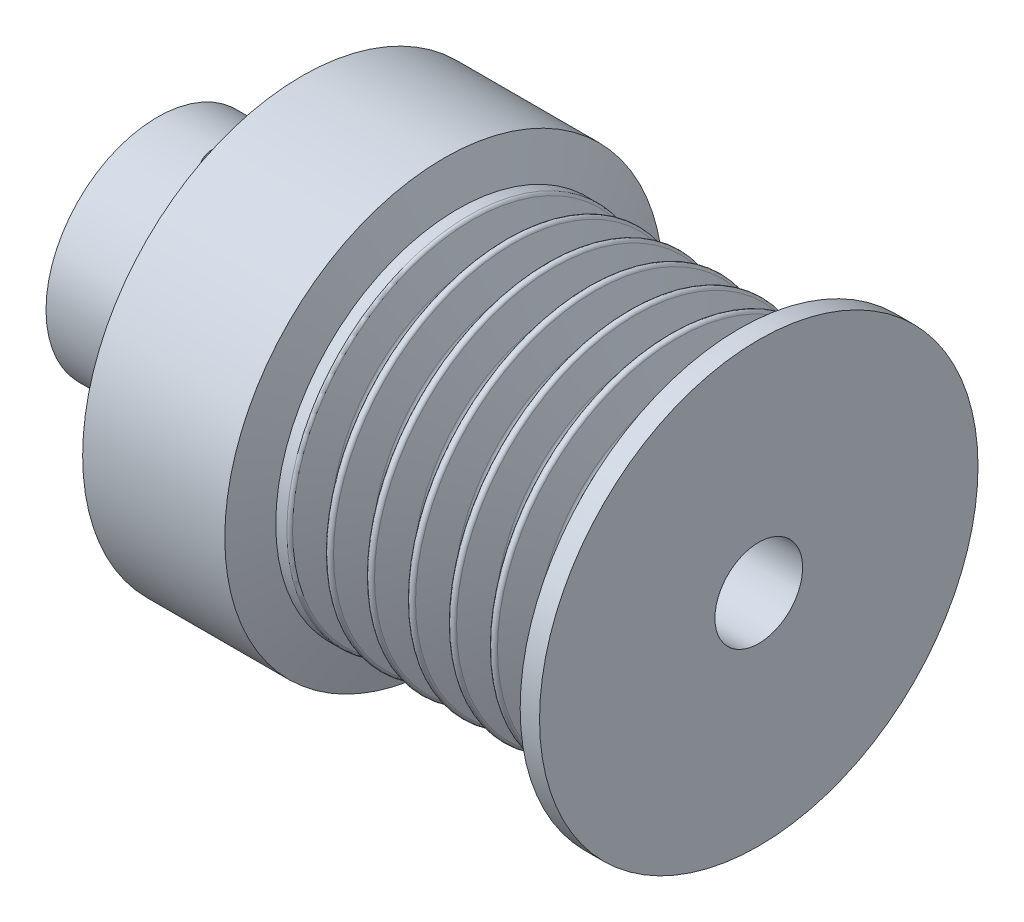
SolidWorks part; units mm, degrees
material "6061-T6 (SS)"
ref_plane "Front Plane" through (0, 0, 0) normal (0, 0, 1) x (1, 0, 0)
ref_plane "Top Plane" through (0, 0, 0) normal (0, 1, 0) x (1, 0, 0)
ref_plane "Right Plane" through (0, 0, 0) normal (1, 0, 0) x (0, 0, -1)
sketch "Sketch1" plane through (0, 0, 0) normal (0, 0, 1) x (1, 0, 0)
  line L0 (0, 0) -> (0, 2.5) construction
  line L1 (0, 2.5) -> (34.29, 2.5)
  line L2 (34.29, 2.5) -> (34.29, 12.5)
  line L3 (34.29, 12.5) -> (8.24, 12.5)
  line L4 (8.24, 12.5) -> (8.24, 6.35)
  line L5 (0, 0) -> (13.5959, 0) construction
  line L8 (8.24, 6.35) -> (0, 6.35)
  line L9 (0, 6.35) -> (0, 2.5)
  dimension "D1" = 25
  dimension "D2" = 5
  dimension "D3" = 26.05
  dimension "D6" = 12.7
  dimension "D7" = 8.24
revolve "Revolve1" add sketch "Sketch1" angle 360 about L5
sketch "Sketch2" plane through (0, 0, 0) normal (0, 0, 1) x (1, 0, 0)
  line L0 (29.4386, 12.5) -> (29.4386, 10.3699)
  line L2 (29.6295, 10.2362) -> (30.2251, 8.5999)
  line L3 (30.9889, 8.5999) -> (31.5845, 10.2362)
  line L4 (31.7754, 10.3699) -> (31.7754, 12.5)
  line L5 (31.7754, 12.5) -> (29.4386, 12.5)
  line L6 (29.4386, 11.43) -> (31.7754, 11.43) construction
  line L7 (15.24, 0) -> (34.29, 0) construction
  line L8 (29.6295, 10.2362) -> (31.5845, 10.2362) construction
  line L9 (29.4386, 12.5) -> (27.1018, 12.5) construction
  line L10 (34.29, 12.5) -> (8.24, 12.5) construction
  line L11 (27.1018, 12.5) -> (24.765, 12.5) construction
  line L13 (24.765, 0) -> (24.765, 12.5) construction
  line L15 (34.29, -12.5) -> (34.29, 12.5) construction
  line L16 (8.24, 12.5) -> (8.24, -12.5) construction
  arc A0 (29.4386, 10.3699) -> (29.6295, 10.2362) centre (29.4386, 10.1667) cw
  arc A1 (30.2251, 8.5999) -> (30.9889, 8.5999) centre (30.607, 8.7389) ccw
  arc A2 (31.5845, 10.2362) -> (31.7754, 10.3699) centre (31.7754, 10.1667) cw
  dimension "D1" = 0.4064
  dimension "D5" = 0.2032
  dimension "D2" = 2.3368
  dimension "D4" = 1.1938
  dimension "D6" = 40
  dimension "D3" = 7
  dimension "D7" = 11.43
revolve "Cut-Revolve1" cut sketch "Sketch2" angle 360 about L7
pattern_linear "LPattern1" count 6 spacing 2.3368 along (-1, 0, 0) of "Cut-Revolve1"
sketch "Sketch3" plane through (0, 0, 0) normal (0, 0, 1) x (1, 0, 0)
  line L0 (31.7754, 12.5) -> (33.1857, 12.5)
  line L1 (34.29, 12.5) -> (31.7754, 12.5) construction
  line L2 (33.1857, 12.5) -> (32.4104, 10.3699)
  line L3 (32.4104, 10.3699) -> (31.7754, 10.3699)
  line L4 (31.7754, 12.5) -> (31.7754, -12.5) construction
  line L5 (31.7754, 10.3699) -> (31.7754, 12.5)
  line L6 (31.7754, 10.3699) -> (31.7754, -10.3699) construction
  line L7 (30.607, 8.3325) -> (30.607, 11.4458) construction
  line L8 (24.765, 10.3699) -> (24.765, 14.7012) construction
  line L9 (17.7546, 10.3699) -> (17.7546, 12.5)
  line L10 (17.1196, 10.3699) -> (17.7546, 10.3699)
  line L11 (16.3443, 12.5) -> (17.1196, 10.3699)
  line L12 (17.7546, 12.5) -> (16.3443, 12.5)
  line L13 (0, 0) -> (26.9583, 0) construction
  arc A0 (30.2251, 8.5999) -> (30.9889, 8.5999) centre (30.607, 8.7389) ccw construction
  arc A1 (24.9559, 10.2362) -> (24.5741, 10.2362) centre (24.765, 10.1667) ccw construction
  dimension "D1" = 1.8034
  dimension "D2" = 20
revolve "Cut-Revolve2" cut sketch "Sketch3" angle 360 about L13
fillet "Fillet1" radius 0.762 1 edges at (8.24, 0, 6.35)
ref_plane "Plane1" through (0, 6.35, 0) normal (0, 1, 0) x (1, 0, 0)
sketch "Sketch6" plane through (0, 6.35, 0) normal (0, 1, 0) x (1, 0, 0)
  line L1 (5.065, 0) -> (0, 0) construction
  line L6 (8.24, 12.5) -> (8.24, -12.5) construction
  circle A0 centre (5.065, 0) radius 3.175 construction
  point P0 (5.065, 0)
  dimension "D1" = 6.35
hole_wizard "#10-24 Tapped Hole1" positions "Sketch6" profile "Sketch5" tap size "#10-24" standard "ANSI Inch" end condition up to next
sketch "Sketch5" plane through (5.065, 6.35, 0) normal (1, 0, 0) x (0, 0, 1)
  line L0 (0, 0) -> (0, 3.85)
  line L1 (0, 3.85) -> (1.8986, 3.85)
  line L2 (1.8986, 3.85) -> (1.8986, 0)
  line L5 (1.8986, 0) -> (0, 0)
  line L11 (0, -6.35) -> (0, 107.95) construction
  dimension "Thru Tap Drill Dia." = 3.7973
  dimension "Thru Tap Drill Depth" = 3.85
ref_plane "Plane2" through (17.7546, 0, 0) normal (1, 0, 0) x (0, 0, -1)
ref_plane "Plane3" through (31.7754, 0, 0) normal (1, 0, 0) x (0, 0, -1)
equation "\"D2@Sketch1\"=5mm"
equation "\"D3@Sketch2\"=7mm"
equation "\"D4@Sketch2\"=0.094in/2"
equation "\"D1@Sketch1\"=25mm"
equation "\"D3@Sketch1\"=0.75in+7mm"
equation "\"D7@Sketch2\"=0.9in/2"
equation "\"D7@Sketch1\"=0.60in-7mm"
